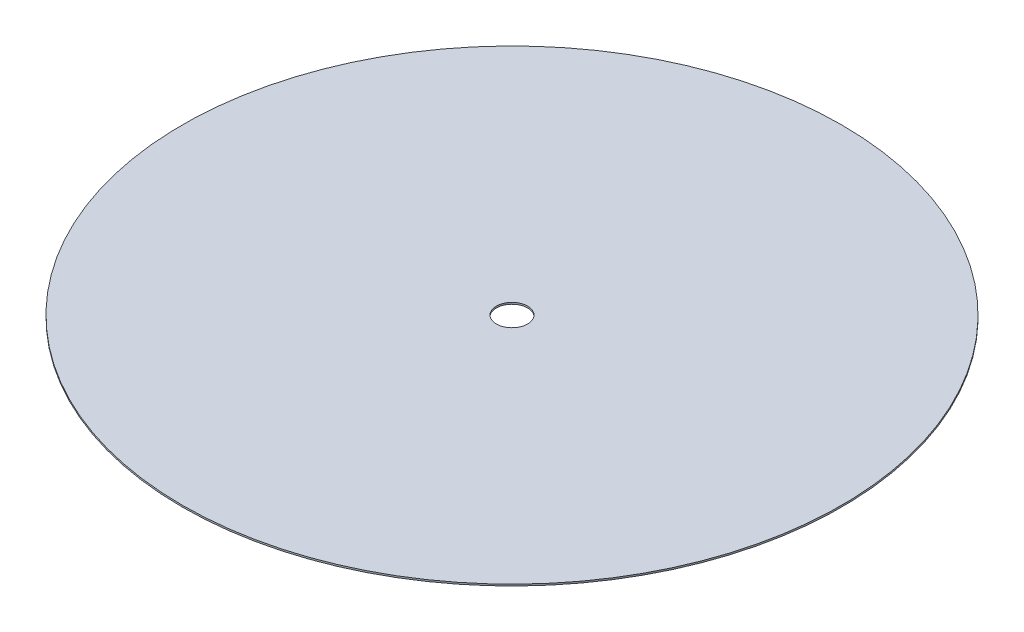
SolidWorks part; units mm, degrees
ref_plane "Alzado" through (0, 0, 0) normal (0, 0, 1) x (1, 0, 0)
ref_plane "Planta" through (0, 0, 0) normal (0, 1, 0) x (1, 0, 0)
ref_plane "Vista lateral" through (0, 0, 0) normal (1, 0, 0) x (0, 0, -1)
sketch "Croquis1" plane through (0, 0, 0) normal (0, 1, 0) x (1, 0, 0)
  circle A0 centre (0, 0) radius 403.28
  circle A1 centre (0, 0) radius 19.05
  dimension "D1" = 38.1
  dimension "D2" = 806.56
extrude "Saliente-Extruir1" add sketch "Croquis1" along normal blind 2
sketch "Croquis2" plane through (0, 2, 0) normal (0, 1, 0) x (1, 0, 0)
  line L0 (402.1626, 30) -> (317.3098, 30)
  line L1 (317.3098, 30) -> (317.3098, -30)
  line L2 (317.3098, -30) -> (402.1626, -30)
  line L3 (402.1626, -30) -> (402.1626, 30)
  line L4 (0, 0) -> (317.3098, 0) construction
  line L5 (30, -402.1626) -> (30, -317.3098)
  line L6 (30, -317.3098) -> (-30, -317.3098)
  line L7 (-30, -317.3098) -> (-30, -402.1626)
  line L8 (-30, -402.1626) -> (30, -402.1626)
  line L9 (-402.1626, -30) -> (-317.3098, -30)
  line L10 (-317.3098, -30) -> (-317.3098, 30)
  line L11 (-317.3098, 30) -> (-402.1626, 30)
  line L12 (-402.1626, 30) -> (-402.1626, -30)
  line L13 (-30, 402.1626) -> (-30, 317.3098)
  line L14 (-30, 317.3098) -> (30, 317.3098)
  line L15 (30, 317.3098) -> (30, 402.1626)
  line L16 (30, 402.1626) -> (-30, 402.1626)
  line L17 (0, 0) -> (0, 317.3098) construction
  line L18 (0, 0) -> (-317.3098, 0) construction
  line L19 (0, 0) -> (0, -317.3098) construction
  circle A0 centre (0, 0) radius 403.28 construction
  point P6 (0, 0)
  point P10 (402.1626, 0)
  point P19 (0, -402.1626)
  point P24 (-402.1626, 0)
  point P29 (0, 402.1626)
  point P30 (0, 0)
  dimension "D1" = 84.8528
  dimension "D2" = 60
  dimension "D3" = 4
sketch "Croquis3" plane through (0, 2, 0) normal (0, 1, 0) x (1, 0, 0)
  line L0 (402.1626, 30) -> (342.1626, 30)
  line L1 (342.1626, 30) -> (342.1626, -30)
  line L2 (342.1626, -30) -> (402.1626, -30)
  line L3 (402.1626, -30) -> (402.1626, 30)
  line L4 (0, 0) -> (342.1626, 0) construction
  line L19 (30, -402.1626) -> (30, -342.1626)
  line L20 (30, -342.1626) -> (-30, -342.1626)
  line L21 (-30, -342.1626) -> (-30, -402.1626)
  line L22 (-30, -402.1626) -> (30, -402.1626)
  line L23 (0, 0) -> (0, -342.1626) construction
  line L24 (-402.1626, -30) -> (-342.1626, -30)
  line L25 (-342.1626, -30) -> (-342.1626, 30)
  line L26 (-342.1626, 30) -> (-402.1626, 30)
  line L27 (-402.1626, 30) -> (-402.1626, -30)
  line L28 (0, 0) -> (-342.1626, 0) construction
  line L29 (-30, 402.1626) -> (-30, 342.1626)
  line L30 (-30, 342.1626) -> (30, 342.1626)
  line L31 (30, 342.1626) -> (30, 402.1626)
  line L32 (30, 402.1626) -> (-30, 402.1626)
  line L33 (0, 0) -> (0, 342.1626) construction
  circle A2 centre (0, 0) radius 403.28 construction
  point P6 (0, 0)
  point P8 (402.1626, 0)
  point P19 (0, -402.1626)
  point P25 (-402.1626, 0)
  point P34 (0, 402.1626)
  point P35 (0, 0)
  dimension "D1" = 806.56
  dimension "D2" = 60
  dimension "D3" = 4
  dimension "D4" = 60
